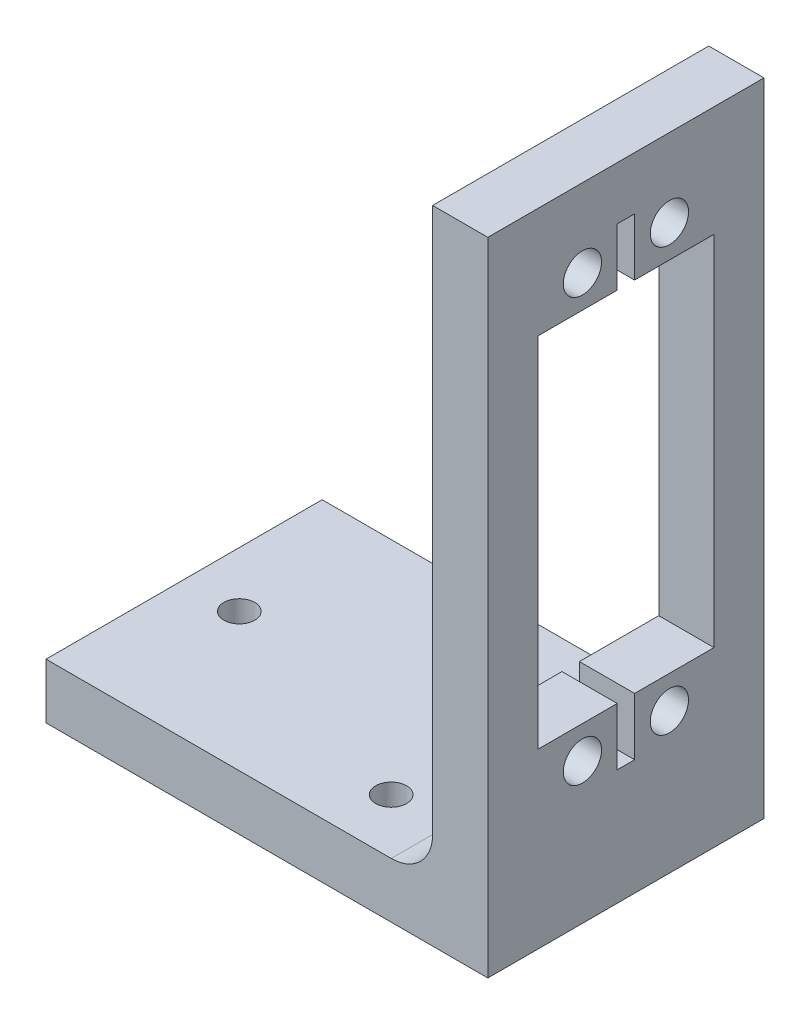
SolidWorks part; units mm, degrees
ref_plane "Front Plane" through (0, 0, 0) normal (0, 0, 1) x (1, 0, 0)
ref_plane "Top Plane" through (0, 0, 0) normal (0, 1, 0) x (1, 0, 0)
ref_plane "Right Plane" through (0, 0, 0) normal (1, 0, 0) x (0, 0, -1)
sketch "Sketch3" plane through (0, 0, 0) normal (1, 0, 0) x (0, 0, -1)
  line L0 (5.748, 54.704) -> (26.002, 13.55) construction
  line L1 (0, 0) -> (31.75, 0)
  line L2 (0, 0) -> (0, 67.404)
  line L3 (0, 67.404) -> (31.75, 67.404)
  line L4 (31.75, 0) -> (31.75, 67.404)
  line L5 (5.748, 54.704) -> (14.875, 54.704)
  line L6 (5.748, 54.704) -> (5.748, 13.55)
  line L7 (5.748, 13.55) -> (14.875, 13.55)
  line L8 (26.002, 54.704) -> (26.002, 13.55)
  line L9 (26.002, 54.704) -> (5.748, 13.55) construction
  line L10 (10.875, 58.427) -> (20.875, 9.827) construction
  line L11 (10.875, 9.827) -> (20.875, 58.427) construction
  line L12 (16.875, 13.55) -> (26.002, 13.55)
  line L13 (14.875, 13.55) -> (14.875, 6.946)
  line L14 (14.875, 6.946) -> (16.875, 6.946)
  line L15 (16.875, 13.55) -> (16.875, 6.946)
  line L16 (15.875, 34.127) -> (-939.9401, 34.127) construction
  line L17 (14.875, 61.308) -> (16.875, 61.308)
  line L18 (14.875, 54.704) -> (14.875, 61.308)
  line L19 (16.875, 54.704) -> (16.875, 61.308)
  line L20 (16.875, 54.704) -> (26.002, 54.704)
  circle A0 centre (10.875, 9.827) radius 2.2
  circle A1 centre (20.875, 9.827) radius 2.2
  circle A2 centre (10.875, 58.427) radius 2.2
  circle A3 centre (20.875, 58.427) radius 2.2
  point P13 (15.875, 6.946)
  point P22 (15.875, 34.127)
  point P23 (15.875, 34.127)
  point P32 (15.875, 44.45)
  point P34 (15.875, 0)
  dimension "D3" = 4.4
  dimension "D1" = 10
  dimension "D2" = 48.6
  dimension "D4" = 41.154
  dimension "D5" = 20.254
  dimension "D6" = 2
  dimension "D7" = 6.604
  dimension "D8" = 30.9
  dimension "D9" = 44.45
  dimension "D10" = 31.75
  dimension "D12" = 12.7
extrude "Boss-Extrude1" add sketch "Sketch3" along normal blind 6.35
sketch "Sketch5" plane through (6.35, 0, 0) normal (1, 0, 0) x (0, 0, -1)
  line L1 (0, 0) -> (31.75, 0)
  line L2 (0, 0) -> (0, -6.35)
  line L3 (0, -6.35) -> (31.75, -6.35)
  line L4 (31.75, 0) -> (31.75, -6.35)
  dimension "D1" = 6.35
extrude "Boss-Extrude2" add sketch "Sketch5" against normal blind 50.8
fillet "Fillet1" radius 4.7625 1 edges at (0, 0, -15.875)
sketch "Sketch6" plane through (0, 0, 0) normal (0, 1, 0) x (1, 0, 0)
  line L0 (-44.45, 0) -> (-4.7625, 0) construction
  line L1 (-4.7625, 0) -> (-4.7625, 31.75) construction
  line L2 (-44.45, 31.75) -> (-44.45, 0) construction
  line L3 (0, 15.875) -> (-33.0413, 15.875) construction
  line L4 (0, 31.75) -> (0, 0) construction
  circle A0 centre (-11.1125, 6.35) radius 1.777
  circle A2 centre (-38.1, 15.875) radius 1.777
  circle A3 centre (-11.1125, 25.4) radius 1.777
  dimension "D1" = 3.554
  dimension "D2" = 6.35
  dimension "D3" = 6.35
  dimension "D4" = 6.35
extrude "Cut-Extrude1" cut sketch "Sketch6" against normal through all
equation "\"D1@Sketch6\" = 3.3mm + \"normTol\""
equation "\"tightTol\"= 0.005in"
equation "\"normTol\"= 0.01in"
equation "\"looseTol\"= 0.02in"
